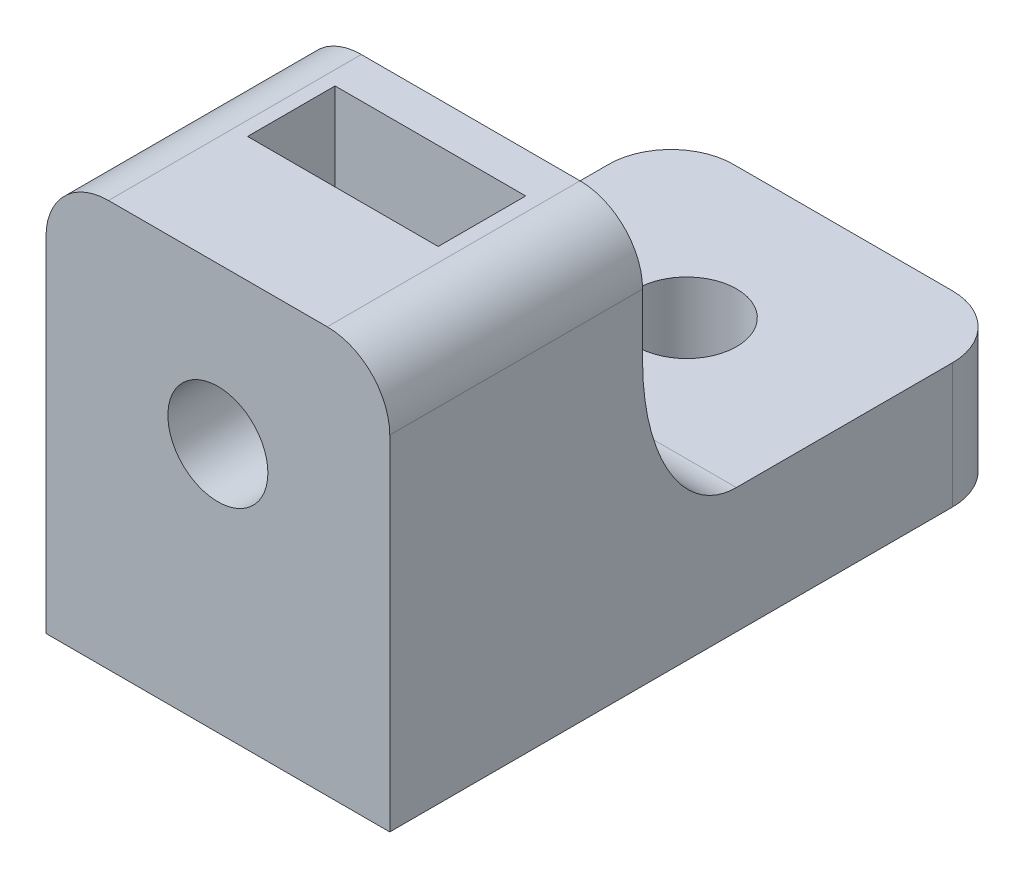
SolidWorks part; units mm, degrees
material "PET-G"
ref_plane "Front Plane" through (0, 0, 0) normal (0, 0, 1) x (1, 0, 0)
ref_plane "Top Plane" through (0, 0, 0) normal (0, 1, 0) x (1, 0, 0)
ref_plane "Right Plane" through (0, 0, 0) normal (1, 0, 0) x (0, 0, -1)
sketch "Sketch1" plane through (0, 0, 0) normal (0, 1, 0) x (1, 0, 0)
  line L0 (5.5, 8.09) -> (-5.5, 8.09)
  line L1 (-5.5, 0) -> (5.5, 0)
  line L2 (-5.5, 0) -> (-5.5, 20)
  line L3 (-5.5, 20) -> (5.5, 20)
  line L4 (5.5, 0) -> (5.5, 20)
  line L6 (3.05, 6.8) -> (-3.05, 6.8)
  line L7 (3.05, 6.8) -> (3.05, 4)
  line L8 (3.05, 4) -> (-3.05, 4)
  line L9 (-3.05, 6.8) -> (-3.05, 4)
  line L10 (3.05, 6.8) -> (-3.05, 4) construction
  line L11 (3.05, 4) -> (-3.05, 6.8) construction
  point P7 (0, 5.4)
  dimension "D1" = 11
  dimension "D2" = 20
  dimension "D3" = 2.8
  dimension "D4" = 4
  dimension "D5" = 6.1
extrude "Base" add sketch "Sketch1" along normal blind 4 contours L3 L4 L1 L2
extrude "VerticalPiece" add sketch "Sketch1<3>" along normal blind 13 contours L1 L4 L0 L2 L9 L6 L7 L8 region at (0, 0, -3.7231)
sketch "Sketch1<3>" plane through (0, 0, 0) normal (0, 1, 0) x (1, 0, 0) same geometry as "Sketch1"
fillet "FilletCorner" radius 3 1 edges at (0, 4, -8.09) second distance 5 first distance on face at (0, 4, -14.045)
hole_wizard "Ø3.2 (3.2) Horizontal Hole" positions "Sketch2" profile "Sketch4" hole size "Ø3.2" standard "ANSI Metric" end condition through all
sketch "Sketch2" plane through (0, 0, 0) normal (0, -1, 0) x (-1, 0, 0)
  line L0 (5.5, 0) -> (-5.5, 0) construction
  point P0 (0, 15)
  dimension "D1" = 15
sketch "Sketch4" plane through (0, 0, -15) normal (1, 0, 0) x (0, 0, -1)
  line L0 (0, 0) -> (0, 13)
  line L1 (0, 13) -> (1.6, 13)
  line L2 (1.6, 13) -> (1.6, 0)
  line L5 (1.6, 0) -> (0, 0)
  line L11 (0, -6.35) -> (0, 107.95) construction
  dimension "Thru Hole Dia." = 3.2
  dimension "Thru Hole Depth" = 13
hole_wizard "Ø3.2 (3.2) Vertical Hole" positions "Sketch5" profile "Sketch6" hole size "Ø3.2" standard "ANSI Metric" end condition through all
sketch "Sketch5" plane through (0, 0, 0) normal (0, 0, 1) x (1, 0, 0)
  line L0 (-5.5, 0) -> (5.5, 0) construction
  point P0 (0, 8)
  dimension "D1" = 8
sketch "Sketch6" plane through (0, 8, 0) normal (1, 0, 0) x (0, -1, 0)
  line L0 (0, 0) -> (0, 20)
  line L1 (0, 20) -> (1.6, 20)
  line L2 (1.6, 20) -> (1.6, 0)
  line L5 (1.6, 0) -> (0, 0)
  line L11 (0, -6.35) -> (0, 107.95) construction
  dimension "Thru Hole Dia." = 3.2
  dimension "Thru Hole Depth" = 20
extrude "NutSlot" add sketch "Sketch1<4>" along normal blind 4.8 contours L6 L9 L8 L7 region at (0, 0, -5.4)
sketch "Sketch1<4>" plane through (0, 0, 0) normal (0, 1, 0) x (1, 0, 0) same geometry as "Sketch1"
fillet "Fillet2" radius 2 4 edges at (5.5, 2, -20) (-5.5, 2, -20) (-5.5, 13, -4.045) (5.5, 13, -4.045)
fillet "ForReference" [suppressed] radius 0.4
